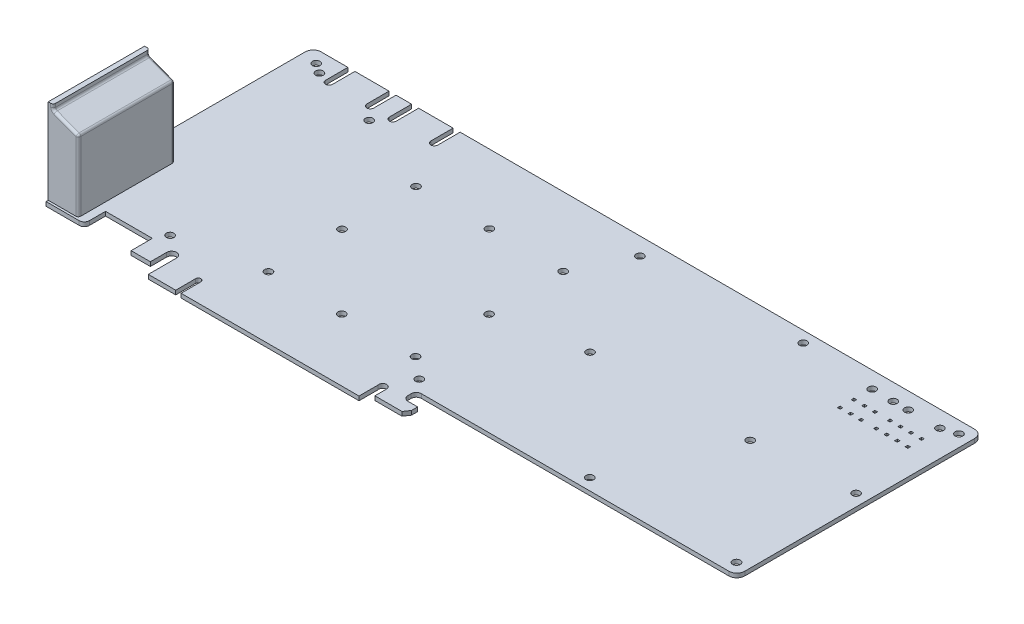
SolidWorks part; units mm, degrees
ref_plane "Front Plane" through (0, 0, 0) normal (0, 0, 1) x (1, 0, 0)
ref_plane "Top Plane" through (0, 0, 0) normal (0, 1, 0) x (1, 0, 0)
ref_plane "Right Plane" through (0, 0, 0) normal (1, 0, 0) x (0, 0, -1)
sketch "Sketch1" plane through (0, 0, 0) normal (0, 1, 0) x (1, 0, 0)
  line L0 (284.8333, 355) -> (1424.1667, 355) construction
sketch "Sketch2" plane through (0, 0, 0) normal (0, 1, 0) x (1, 0, 0)
  line L0 (0, 4.7617) -> (13.2349, 4.7617)
  line L1 (33.9466, 13.2428) -> (43.5947, 13.2428) construction
  line L2 (0, 4.7617) -> (0, 108.1273)
  line L3 (3.175, 111.3023) -> (13.8686, 111.3023)
  line L4 (267.037, 16.4177) -> (267.037, 108.1273)
  line L5 (15.2669, 13.2428) -> (33.9466, 13.2428)
  line L6 (15.2669, 13.2428) -> (15.2669, 6.7937)
  line L7 (41.6225, 4.7617) -> (41.6225, 11.2706)
  line L8 (33.9466, 13.2428) -> (33.9466, 4.7617)
  line L9 (132.6992, 3.2386) -> (143.5323, 3.2386)
  line L10 (143.5323, 3.2386) -> (145.0554, 5.5108)
  line L11 (145.0554, 5.5108) -> (145.0554, 7.927)
  line L12 (145.0554, 7.927) -> (141.2283, 7.927)
  line L13 (139.1963, 9.959) -> (139.1963, 11.2107)
  line L14 (141.2283, 13.2427) -> (263.862, 13.2427)
  line L15 (129.6003, 7.4964) -> (129.6003, 0)
  line L16 (33.9466, 4.7617) -> (41.6225, 4.7617)
  line L17 (45.567, 0) -> (56.4896, 0)
  line L18 (45.567, 11.2706) -> (45.567, 0)
  line L19 (56.4896, 7.927) -> (56.4896, 0)
  line L20 (58.633, 7.927) -> (58.633, 0)
  line L21 (58.633, 0) -> (129.6003, 0)
  line L22 (132.6992, 7.927) -> (132.6992, 3.2386)
  line L23 (16.6652, 102.4034) -> (16.6652, 111.3023)
  line L24 (13.8686, 102.4034) -> (13.8686, 111.3023)
  line L25 (16.6652, 111.3023) -> (30.281, 111.3023)
  line L26 (30.281, 102.4034) -> (30.281, 111.3023)
  line L27 (33.0776, 102.4034) -> (33.0776, 111.3023)
  line L28 (39.2899, 102.4034) -> (39.2899, 111.3023)
  line L29 (42.0865, 102.4034) -> (42.0865, 111.3023)
  line L30 (55.8364, 102.4034) -> (55.8364, 111.3023)
  line L31 (58.633, 102.4034) -> (58.633, 111.3023)
  line L32 (33.0776, 111.3023) -> (39.2899, 111.3023)
  line L33 (42.0865, 111.3023) -> (55.8364, 111.3023)
  line L34 (58.633, 111.3023) -> (263.862, 111.3023)
  arc A0 (45.567, 11.2706) -> (41.6225, 11.2706) centre (43.5947, 11.2706) ccw
  arc A1 (58.633, 7.927) -> (56.4896, 7.927) centre (57.5613, 7.927) ccw
  arc A2 (132.6992, 7.927) -> (129.6003, 7.4964) centre (131.1198, 7.927) ccw
  arc A3 (141.2283, 7.927) -> (139.1963, 9.959) centre (141.2283, 9.959) cw
  arc A4 (139.1963, 11.2107) -> (141.2283, 13.2427) centre (141.2283, 11.2107) cw
  arc A5 (13.2349, 4.7617) -> (15.2669, 6.7937) centre (13.2349, 6.7937) ccw
  arc A6 (0, 108.1273) -> (3.175, 111.3023) centre (3.175, 108.1273) cw
  arc A7 (263.862, 111.3023) -> (267.037, 108.1273) centre (263.862, 108.1273) cw
  arc A8 (263.862, 13.2427) -> (267.037, 16.4177) centre (263.862, 16.4177) ccw
  arc A9 (13.8686, 102.4034) -> (16.6652, 102.4034) centre (15.2669, 102.4034) ccw
  arc A10 (30.281, 102.4034) -> (33.0776, 102.4034) centre (31.6793, 102.4034) ccw
  arc A11 (39.2899, 102.4034) -> (42.0865, 102.4034) centre (40.6882, 102.4034) ccw
  arc A12 (55.8364, 102.4034) -> (58.633, 102.4034) centre (57.2347, 102.4034) ccw
  dimension "D1" = 2.032
  dimension "D2" = 2.032
  dimension "D3" = 3.175
sketch "Sketch3" plane through (0, 0, 0) normal (0, 1, 0) x (1, 0, 0)
  circle A0 centre (6.2136, 106.3109) radius 1.5132
  circle A1 centre (10.179, 103.6334) radius 1.5132
  circle A2 centre (199.902, 106.8691) radius 1.5132
  circle A3 centre (137.2918, 104.3428) radius 1.5132
  circle A4 centre (262.3256, 106.5492) radius 1.5132
  circle A5 centre (262.3256, 65.5208) radius 1.5132
  circle A6 centre (262.3256, 17.8327) radius 1.5132
  circle A7 centre (203.803, 17.8327) radius 1.5132
  circle A8 centre (135.803, 17.8327) radius 1.5132
  circle A9 centre (36.4271, 17.8327) radius 1.5132
  circle A10 centre (36.4271, 97.1969) radius 1.5132
  circle A11 centre (68.6093, 83.7347) radius 1.5132
  circle A12 centre (97.8621, 83.7347) radius 1.5132
  circle A13 centre (127.2798, 83.7347) radius 1.5132
  circle A14 centre (127.2798, 54.2002) radius 1.5132
  circle A15 centre (127.2798, 24.8751) radius 1.5132
  circle A16 centre (97.8621, 24.8751) radius 1.5132
  circle A17 centre (68.6093, 24.8751) radius 1.5132
  circle A18 centre (68.6093, 54.2002) radius 1.5132
  circle A19 centre (160.5528, 61.1867) radius 1.5132
  circle A20 centre (222.9205, 62.6998) radius 1.5132
extrude "Boss-Extrude1" add sketch "Sketch2" along normal blind 1.651
extrude "Cut-Extrude2" cut sketch "Sketch3" along normal through all
sketch "Sketch4" plane through (0, 0, -111.3023) normal (0, 0, -1) x (-1, 0, 0)
  line L0 (-259.28, 1.651) -> (-240.6669, 1.651) construction
  line L1 (-263.862, 1.651) -> (-58.633, 1.651) construction
ref_plane "Plane1" through (259.28, 1.651, -111.3023) normal (-1, 0, 0) x (0, 0, 1)
ref_plane "Plane2" through (240.6669, 0, 0) normal (-1, 0, 0) x (0, 0, 1)
sketch "Sketch5" plane through (0, 0, 0) normal (0, -1, 0) x (1, 0, 0)
  line L0 (229.0319, -92.4373) -> (230.1019, -92.4373)
  line L1 (229.0319, -96.8673) -> (230.1019, -96.8673)
  line L2 (229.0319, -96.8673) -> (229.0319, -97.9373)
  line L3 (229.0319, -97.9373) -> (230.1019, -97.9373)
  line L4 (230.1019, -96.8673) -> (230.1019, -97.9373)
  line L5 (229.0319, -96.8673) -> (230.1019, -97.9373) construction
  line L6 (229.0319, -97.9373) -> (230.1019, -96.8673) construction
  line L7 (230.1019, -91.3673) -> (230.1019, -92.4373)
  line L8 (229.0319, -92.4373) -> (230.1019, -91.3673) construction
  line L9 (229.0319, -91.3673) -> (230.1019, -91.3673)
  line L10 (229.0319, -91.3673) -> (230.1019, -92.4373) construction
  line L11 (229.0319, -91.3673) -> (229.0319, -92.4373)
  line L12 (233.2319, -92.4373) -> (234.3019, -92.4373)
  line L13 (234.3019, -91.3673) -> (234.3019, -92.4373)
  line L14 (233.2319, -92.4373) -> (234.3019, -91.3673) construction
  line L15 (233.2319, -91.3673) -> (234.3019, -91.3673)
  line L16 (233.2319, -91.3673) -> (234.3019, -92.4373) construction
  line L17 (233.2319, -91.3673) -> (233.2319, -92.4373)
  line L18 (237.4319, -92.4373) -> (238.5019, -92.4373)
  line L19 (238.5019, -91.3673) -> (238.5019, -92.4373)
  line L20 (237.4319, -92.4373) -> (238.5019, -91.3673) construction
  line L21 (237.4319, -91.3673) -> (238.5019, -91.3673)
  line L22 (237.4319, -91.3673) -> (238.5019, -92.4373) construction
  line L23 (237.4319, -91.3673) -> (237.4319, -92.4373)
  line L24 (237.4319, -97.9373) -> (238.5019, -97.9373)
  line L25 (238.5019, -96.8673) -> (238.5019, -97.9373)
  line L26 (237.4319, -97.9373) -> (238.5019, -96.8673) construction
  line L27 (237.4319, -96.8673) -> (238.5019, -96.8673)
  line L28 (237.4319, -96.8673) -> (238.5019, -97.9373) construction
  line L29 (237.4319, -96.8673) -> (237.4319, -97.9373)
  line L30 (233.2319, -97.9373) -> (234.3019, -97.9373)
  line L31 (234.3019, -96.8673) -> (234.3019, -97.9373)
  line L32 (233.2319, -97.9373) -> (234.3019, -96.8673) construction
  line L33 (233.2319, -96.8673) -> (234.3019, -96.8673)
  line L34 (233.2319, -96.8673) -> (234.3019, -97.9373) construction
  line L35 (233.2319, -96.8673) -> (233.2319, -97.9373)
  line L36 (243.445, -97.9373) -> (244.515, -97.9373)
  line L37 (244.515, -96.8673) -> (244.515, -97.9373)
  line L38 (243.445, -97.9373) -> (244.515, -96.8673) construction
  line L39 (243.445, -96.8673) -> (244.515, -96.8673)
  line L40 (243.445, -96.8673) -> (244.515, -97.9373) construction
  line L41 (243.445, -96.8673) -> (243.445, -97.9373)
  line L42 (247.645, -97.9373) -> (248.715, -97.9373)
  line L43 (248.715, -96.8673) -> (248.715, -97.9373)
  line L44 (247.645, -97.9373) -> (248.715, -96.8673) construction
  line L45 (247.645, -96.8673) -> (248.715, -96.8673)
  line L46 (247.645, -96.8673) -> (248.715, -97.9373) construction
  line L47 (247.645, -96.8673) -> (247.645, -97.9373)
  line L48 (251.845, -97.9373) -> (252.915, -97.9373)
  line L49 (252.915, -96.8673) -> (252.915, -97.9373)
  line L50 (251.845, -97.9373) -> (252.915, -96.8673) construction
  line L51 (251.845, -96.8673) -> (252.915, -96.8673)
  line L52 (251.845, -96.8673) -> (252.915, -97.9373) construction
  line L53 (251.845, -96.8673) -> (251.845, -97.9373)
  line L54 (256.045, -97.9373) -> (257.115, -97.9373)
  line L55 (257.115, -96.8673) -> (257.115, -97.9373)
  line L56 (256.045, -97.9373) -> (257.115, -96.8673) construction
  line L57 (256.045, -96.8673) -> (257.115, -96.8673)
  line L58 (256.045, -96.8673) -> (257.115, -97.9373) construction
  line L59 (256.045, -96.8673) -> (256.045, -97.9373)
  line L60 (256.045, -92.4373) -> (257.115, -92.4373)
  line L61 (257.115, -91.3673) -> (257.115, -92.4373)
  line L62 (256.045, -92.4373) -> (257.115, -91.3673) construction
  line L63 (256.045, -91.3673) -> (257.115, -91.3673)
  line L64 (256.045, -91.3673) -> (257.115, -92.4373) construction
  line L65 (256.045, -91.3673) -> (256.045, -92.4373)
  line L66 (251.845, -92.4373) -> (252.915, -92.4373)
  line L67 (252.915, -91.3673) -> (252.915, -92.4373)
  line L68 (251.845, -92.4373) -> (252.915, -91.3673) construction
  line L69 (251.845, -91.3673) -> (252.915, -91.3673)
  line L70 (251.845, -91.3673) -> (252.915, -92.4373) construction
  line L71 (251.845, -91.3673) -> (251.845, -92.4373)
  line L72 (247.645, -92.4373) -> (248.715, -92.4373)
  line L73 (248.715, -91.3673) -> (248.715, -92.4373)
  line L74 (247.645, -92.4373) -> (248.715, -91.3673) construction
  line L75 (247.645, -91.3673) -> (248.715, -91.3673)
  line L76 (247.645, -91.3673) -> (248.715, -92.4373) construction
  line L77 (247.645, -91.3673) -> (247.645, -92.4373)
  line L78 (243.445, -92.4373) -> (244.515, -92.4373)
  line L79 (244.515, -91.3673) -> (244.515, -92.4373)
  line L80 (243.445, -92.4373) -> (244.515, -91.3673) construction
  line L81 (243.445, -91.3673) -> (244.515, -91.3673)
  line L82 (243.445, -91.3673) -> (244.515, -92.4373) construction
  line L83 (243.445, -91.3673) -> (243.445, -92.4373)
  circle A0 centre (229.5669, -104.7023) radius 1.5
  circle A1 centre (237.9669, -104.7023) radius 1.5
  circle A2 centre (243.98, -104.7023) radius 1.5
  circle A3 centre (256.58, -104.7023) radius 1.5
  point P9 (229.5669, -97.4023)
  point P15 (229.5669, -91.9023)
  point P20 (233.7669, -91.9023)
  point P25 (237.9669, -91.9023)
  point P30 (237.9669, -97.4023)
  point P35 (233.7669, -97.4023)
  point P40 (243.98, -97.4023)
  point P45 (248.18, -97.4023)
  point P50 (252.38, -97.4023)
  point P55 (256.58, -97.4023)
  point P60 (256.58, -91.9023)
  point P65 (252.38, -91.9023)
  point P70 (248.18, -91.9023)
  point P75 (243.98, -91.9023)
  dimension "D1" = 3
  dimension "D2" = 3
  dimension "D3" = 3
  dimension "D4" = 3
extrude "Cut-Extrude3" cut sketch "Sketch5" against normal up to surface (1.651 mm away) up to face at (160.5528, 1.651, -59.6735)
sketch "Sketch8" plane through (0, 1.651, 0) normal (0, 1, 0) x (1, 0, 0)
  line L0 (0, 108.1273) -> (0, 4.7617) construction
  line L1 (0, 5.6351) -> (12.0152, 5.6351)
  line L2 (0, 5.6351) -> (0, 44.0864)
  line L3 (0, 44.0864) -> (12.0152, 44.0864)
  line L4 (12.0152, 5.6351) -> (12.0152, 44.0864)
extrude "Boss-Extrude2" add sketch "Sketch8" along normal blind 34 separate body
sketch "Sketch9" plane through (0, 0, -5.6351) normal (0, 0, 1) x (1, 0, 0)
  line L0 (12.0152, 29.8839) -> (2, 33.6025)
  line L1 (12.0152, 35.651) -> (12.0152, 1.651) construction
  line L2 (2, 14.2891) -> (2, 33.7198) construction
  line L3 (2, 33.6025) -> (2, 36.2678)
  line L4 (2, 36.2678) -> (12.0152, 36.2678)
  line L6 (12.0152, 36.2678) -> (12.0152, 29.8839)
extrude "Cut-Extrude5" cut sketch "Sketch9" against normal up to surface (38.4512 mm away) up to face at (6.0076, 18.651, -44.0864)
fillet "Fillet1" radius 1 8 edges at (2, 34.6268, -44.0864) (2, 34.6268, -5.6351) (12.0152, 15.7674, -44.0864) (7.0076, 31.7432, -44.0864) (7.0076, 31.7432, -5.6351) (12.0152, 15.7674, -5.6351) (2, 33.6025, -24.8607) (12.0152, 29.8839, -24.8607)
shell "Shell2" thickness 0.5 removed face at (0, 18.651, -24.8607) removed face at (7.7458, 1.651, -24.8607) removed face at (3.72, 24.3299, -44.0864)
